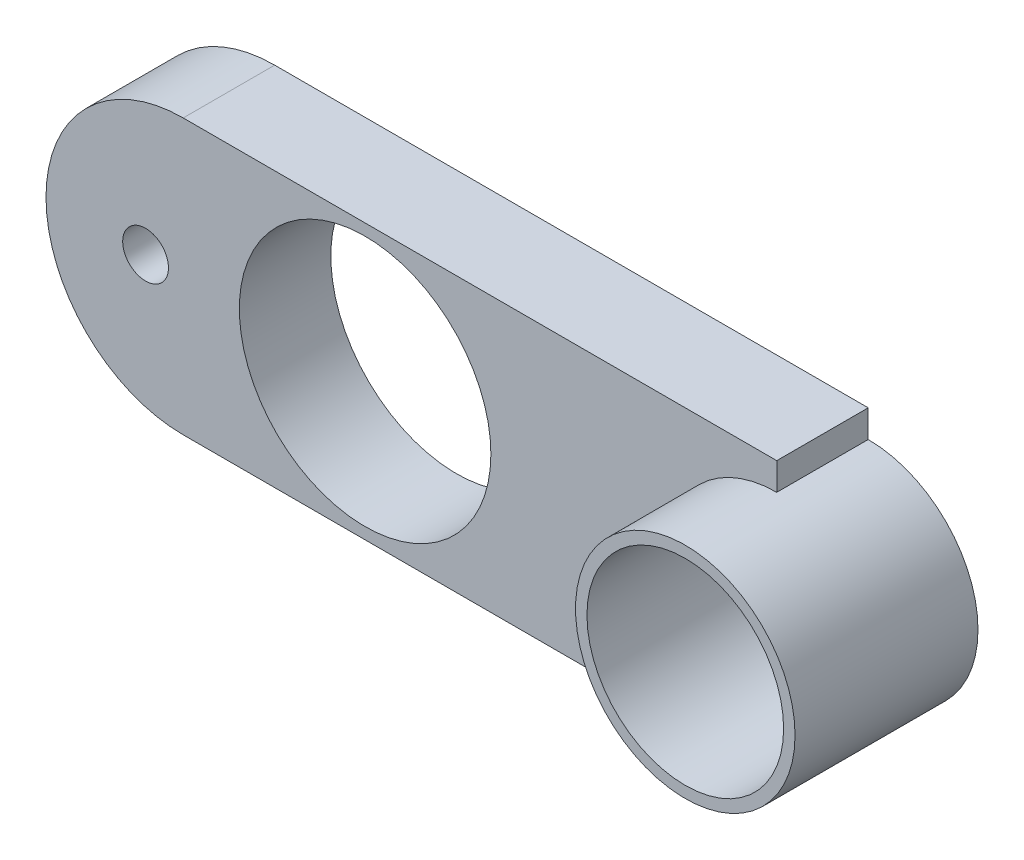
SolidWorks part; units mm, degrees
ref_plane "Front Plane" through (0, 0, 0) normal (0, 0, 1) x (1, 0, 0)
ref_plane "Top Plane" through (0, 0, 0) normal (0, 1, 0) x (1, 0, 0)
ref_plane "Right Plane" through (0, 0, 0) normal (1, 0, 0) x (0, 0, -1)
sketch "Sketch1" plane through (0, 0, 0) normal (0, 0, 1) x (1, 0, 0)
  circle A0 centre (0, 0) radius 30
  dimension "D1" = 60
extrude "Boss-Extrude1" add sketch "Sketch1" along normal blind 20
sketch "Sketch2" plane through (0, 0, 20) normal (0, 0, 1) x (1, 0, 0)
  circle A0 centre (0, 0) radius 27.5
  dimension "D1" = 55
extrude "Cut-Extrude1" cut sketch "Sketch2" against normal through all
ref_plane "Plane1" through (0, 0, 20) normal (0, 0, 1) x (1, 0, 0)
sketch "Sketch4" plane through (0, 0, 20) normal (0, 0, 1) x (1, 0, 0)
  line L0 (0, 30) -> (90, 30)
  line L1 (90, 30) -> (90, 24)
  line L2 (0, -30) -> (90, -30)
  line L3 (90, -30) -> (90, -24)
  arc A0 (90, -24) -> (90, 24) centre (90, 0) ccw
  circle A1 centre (0, 0) radius 30 construction
  arc A2 (0, -30) -> (0, 30) centre (0, 0) ccw
  dimension "D1" = 48
  dimension "D2" = 90
extrude "Boss-Extrude2" add sketch "Sketch4" against normal blind 20
sketch "Sketch6" plane through (0, 0, 20) normal (0, 0, 1) x (1, 0, 0)
  circle A0 centre (90, 0) radius 21.5
  dimension "D1" = 43
extrude "Cut-Extrude2" cut sketch "Sketch6" against normal blind 35
sketch "Sketch11" plane through (0, 0, 20) normal (0, 0, 1) x (1, 0, 0)
  circle A0 centre (90, 0) radius 24
extrude "Boss-Extrude3" add sketch "Sketch11" along normal blind 20
sketch "Sketch12" plane through (0, 0, 40) normal (0, 0, 1) x (1, 0, 0)
  circle A0 centre (90, 0) radius 24
extrude "Boss-Extrude4" add sketch "Sketch12" against normal blind 40
sketch "Sketch13" plane through (0, 0, 40) normal (0, 0, 1) x (1, 0, 0)
  circle A0 centre (90, 0) radius 21.5
  circle A1 centre (90, 0) radius 24 construction
  dimension "D1" = 0
extrude "Cut-Extrude6" cut sketch "Sketch13" against normal blind 35
sketch "Sketch14" plane through (0, 0, 20) normal (0, 0, 1) x (1, 0, 0)
  line L0 (0, -30) -> (-69.77, -30)
  line L1 (-69.77, -30) -> (-69.77, 30)
  line L2 (-69.77, 30) -> (0, 30)
  line L7 (90, 24) -> (90, 30)
  line L8 (90, 30) -> (0, 30)
  line L9 (0, -30) -> (90, -30)
  line L10 (90, -30) -> (90, -24)
  line L11 (90, 24) -> (90, 30)
  line L12 (90, 30) -> (0, 30)
  line L13 (0, -30) -> (90, -30)
  line L14 (90, -30) -> (90, -24)
  arc A0 (0, 30) -> (0, -30) centre (0, 0) ccw
  arc A1 (0, 30) -> (0, -30) centre (0, 0) ccw
  arc A2 (90, 24) -> (90, -24) centre (90, 0) ccw
  arc A3 (0, 30) -> (0, -30) centre (0, 0) ccw
  arc A4 (90, 24) -> (90, -24) centre (90, 0) ccw
  arc A5 (0, 30) -> (0, -30) centre (0, 0) ccw
  arc A6 (0, 30) -> (0, -30) centre (0, 0) ccw
  dimension "D1" = 0
extrude "Boss-Extrude6" add sketch "Sketch14" against normal blind 20 contours A0 L2 L1 L0
sketch "Sketch15" plane through (0, 0, 20) normal (0, 0, 1) x (1, 0, 0)
  circle A0 centre (-48, 0) radius 5
  circle A1 centre (0, 0) radius 27.5 construction
  dimension "D2" = 48
extrude "Cut-Extrude8" cut sketch "Sketch15" against normal blind 20 contours A0
fillet "Fillet1" radius 30 1 edges at (-69.77, -30, 10)
fillet "Fillet2" radius 30 3 edges at (-69.77, 30, 10) (-69.77, 15, 20) (-69.77, 15, 0)
